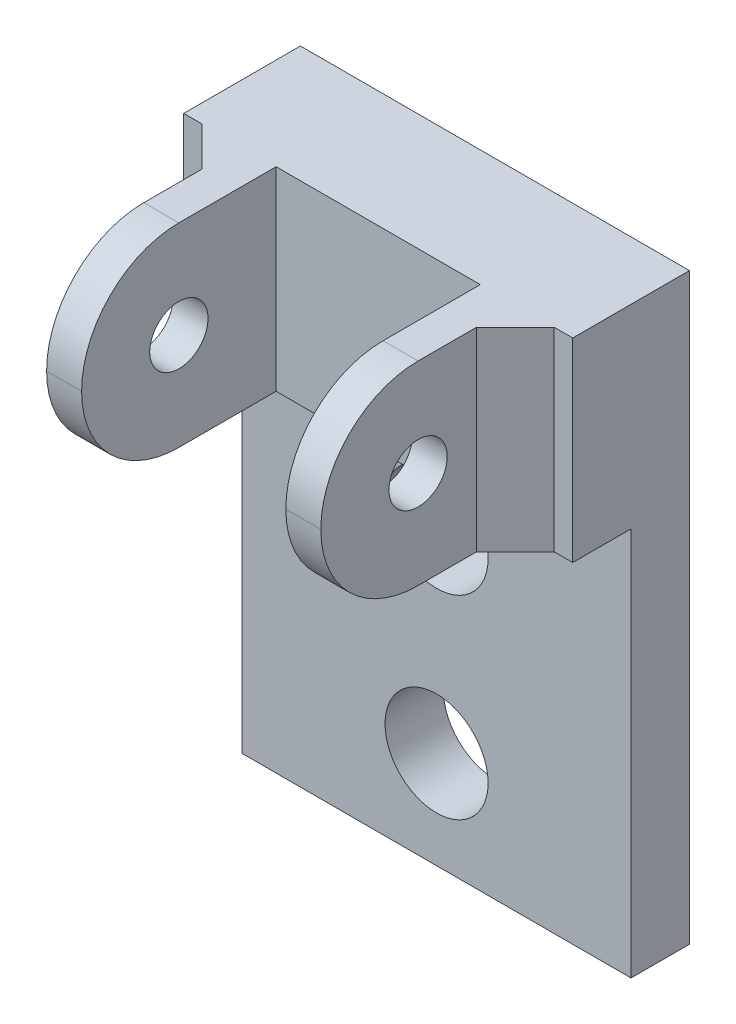
SolidWorks part; units mm, degrees
ref_plane "Front Plane" through (0, 0, 0) normal (0, 0, 1) x (1, 0, 0)
ref_plane "Top Plane" through (0, 0, 0) normal (0, 1, 0) x (1, 0, 0)
ref_plane "Right Plane" through (0, 0, 0) normal (1, 0, 0) x (0, 0, -1)
sketch "Sketch1" plane through (0, 0, 0) normal (0, 0, 1) x (1, 0, 0)
  line L1 (10, -15) -> (-10, -15)
  line L2 (10, -15) -> (10, 15)
  line L3 (10, 15) -> (-10, 15)
  line L4 (-10, -15) -> (-10, 15)
  line L5 (10, -15) -> (-10, 15) construction
  line L6 (10, 15) -> (-10, -15) construction
  circle A0 centre (0, -10) radius 2.65
  circle A1 centre (0, 0) radius 2.65
  point P0 (0, 0)
  point P10 (0, 0)
  dimension "D3" = 5.3
  dimension "D4" = 5.3
  dimension "D5" = 5
  dimension "D6" = 10
  dimension "D1" = 20
  dimension "D2" = 30
extrude "Boss-Extrude1" add sketch "Sketch1" along normal blind 3
sketch "Sketch2" plane through (0, 0, 3) normal (0, 0, 1) x (1, 0, 0)
  line L0 (10, -15) -> (10, 15) construction
  line L1 (-10, 15) -> (10, 15)
  line L2 (-10, 15) -> (-10, 5)
  line L3 (-10, 5) -> (10, 5)
  line L4 (10, 15) -> (10, 5)
  dimension "D1" = 10
extrude "Boss-Extrude2" add sketch "Sketch2" along normal blind 3
sketch "Sketch3" plane through (0, 0, 6) normal (0, 0, 1) x (1, 0, 0)
  line L0 (10, 15) -> (-10, 15) construction
  line L1 (-7.05, 15) -> (-5.25, 15)
  line L2 (-7.05, 15) -> (-7.05, 5)
  line L3 (-7.05, 5) -> (-5.25, 5)
  line L4 (-5.25, 15) -> (-5.25, 5)
  line L5 (-10, 5) -> (10, 5) construction
  line L6 (-10, 15) -> (-10, 5) construction
  line L7 (5.25, 15) -> (7.05, 15)
  line L8 (5.25, 15) -> (5.25, 5)
  line L9 (5.25, 5) -> (7.05, 5)
  line L10 (7.05, 15) -> (7.05, 5)
  dimension "D1" = 10.5
  dimension "D2" = 1.8
  dimension "D3" = 2.95
extrude "Boss-Extrude3" add sketch "Sketch3" along normal blind 10
fillet "Fillet1" radius 5 4 edges at (6.15, 5, 16) (-6.15, 5, 16) (6.15, 15, 16) (-6.15, 15, 16)
sketch "Sketch4" plane through (-7.05, 0, 0) normal (-1, 0, 0) x (0, 0, 1)
  circle A0 centre (11, 10) radius 1.5
  arc A1 (16, 10) -> (11, 15) centre (11, 10) ccw construction
  dimension "D1" = 3
extrude "Cut-Extrude1" cut sketch "Sketch4" against normal up to surface (14.1 mm away) up to face at (7.05, 10, 10.4142)
chamfer "Chamfer1" distance 2 angle 45 2 edges at (7.05, 10, 6) (-7.05, 10, 6)
